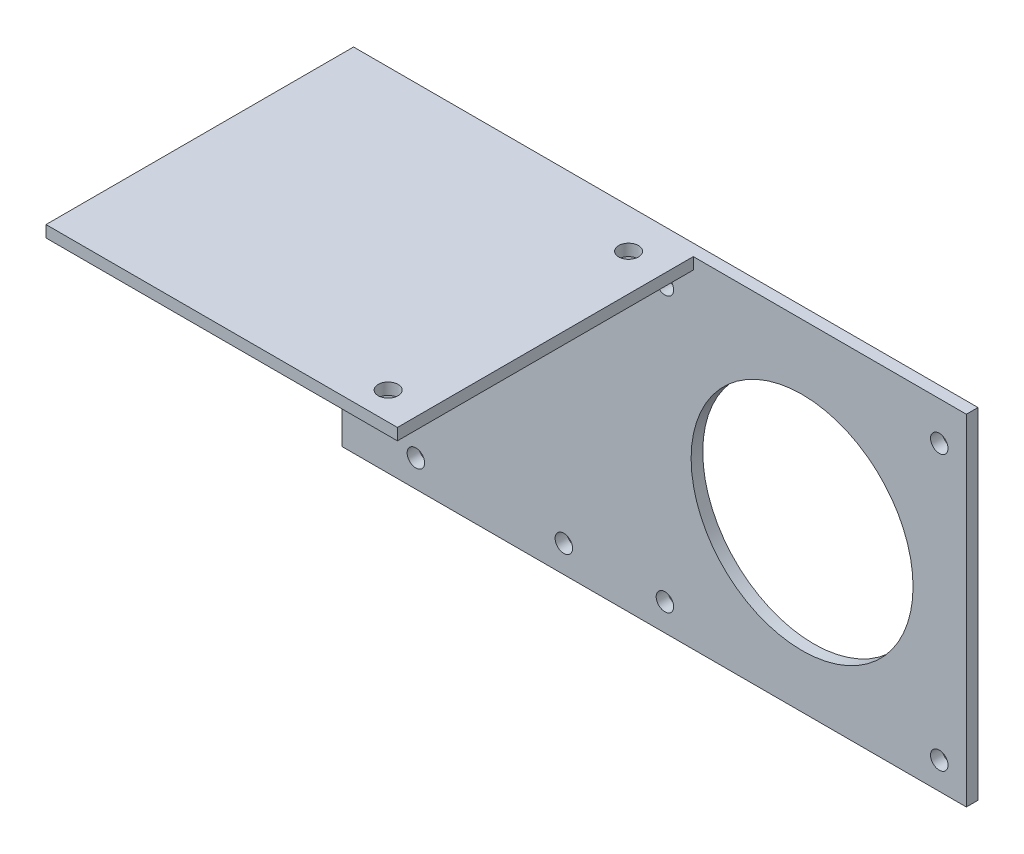
SolidWorks part; units mm, degrees
ref_plane "Front Plane" through (0, 0, 0) normal (0, 0, 1) x (1, 0, 0)
ref_plane "Top Plane" through (0, 0, 0) normal (0, 1, 0) x (1, 0, 0)
ref_plane "Right Plane" through (0, 0, 0) normal (1, 0, 0) x (0, 0, -1)
sketch "Sketch1" plane through (0, 0, 0) normal (0, 0, 1) x (1, 0, 0)
  line L0 (102.55, 51.75) -> (12.7, 51.75) construction
  line L1 (0, 58.4) -> (107.2, 58.4)
  line L2 (0, 58.4) -> (0, 0)
  line L3 (0, 0) -> (107.2, 0)
  line L4 (107.2, 58.4) -> (107.2, 0)
  line L5 (102.55, 51.75) -> (102.55, 4.65) construction
  line L6 (12.7, 51.75) -> (12.7, 4.65) construction
  line L7 (55.45, 4.65) -> (55.45, 51.75) construction
  line L8 (12.7, 4.65) -> (102.55, 4.65) construction
  line L9 (38.1, 51.75) -> (38.1, 4.65) construction
  line L10 (55.45, 51.75) -> (102.55, 4.65) construction
  line L11 (102.55, 51.75) -> (55.45, 4.65) construction
  circle A0 centre (102.55, 51.75) radius 1.5
  circle A1 centre (102.55, 4.65) radius 1.5
  circle A2 centre (55.45, 4.65) radius 1.5
  circle A3 centre (55.45, 51.75) radius 1.5
  circle A4 centre (12.7, 51.75) radius 1.5
  circle A5 centre (38.1, 51.75) radius 1.5
  circle A6 centre (12.7, 4.65) radius 1.5
  circle A7 centre (38.1, 4.65) radius 1.5
  circle A8 centre (79, 28.2) radius 19.05
  dimension "D3" = 3
  dimension "D10" = 38.1
  dimension "D1" = 58.4
  dimension "D2" = 107.2
  dimension "D4" = 47.1
  dimension "D5" = 47.1
  dimension "D6" = 4.65
  dimension "D7" = 25.4
  dimension "D8" = 4.65
  dimension "D9" = 12.7
extrude "Boss-Extrude1" add sketch "Sketch1" against normal blind 2
sketch "Sketch2" plane through (0, 0, -2) normal (0, 0, -1) x (-1, 0, 0)
  line L0 (0, 58.4) -> (0, 56.4)
  line L1 (0, 58.4) -> (0, 0) construction
  line L2 (0, 56.4) -> (-60.325, 56.4)
  line L3 (-60.325, 56.4) -> (-60.325, 58.4)
  line L4 (-107.2, 58.4) -> (0, 58.4) construction
  line L5 (-60.325, 58.4) -> (0, 58.4)
  dimension "D1" = 60.325
  dimension "D2" = 2
extrude "Boss-Extrude2" add sketch "Sketch2" against normal blind 52.8
sketch "Sketch3" plane through (0, 58.4, 0) normal (0, 1, 0) x (1, 0, 0)
  line L0 (53.975, -4.7625) -> (53.975, -46.0375) construction
  line L2 (60.325, -50.8) -> (60.325, 0) construction
  line L3 (0, -50.8) -> (60.325, -50.8) construction
  circle A0 centre (53.975, -4.7625) radius 1.7
  circle A1 centre (53.975, -46.0375) radius 1.7
  point P4 (53.6, -5.4107)
  point P5 (0, 0)
  dimension "D1" = 3.4
  dimension "D2" = 41.275
  dimension "D3" = 4.7625
  dimension "D4" = 6.35
extrude "Cut-Extrude1" cut sketch "Sketch3" against normal through all
